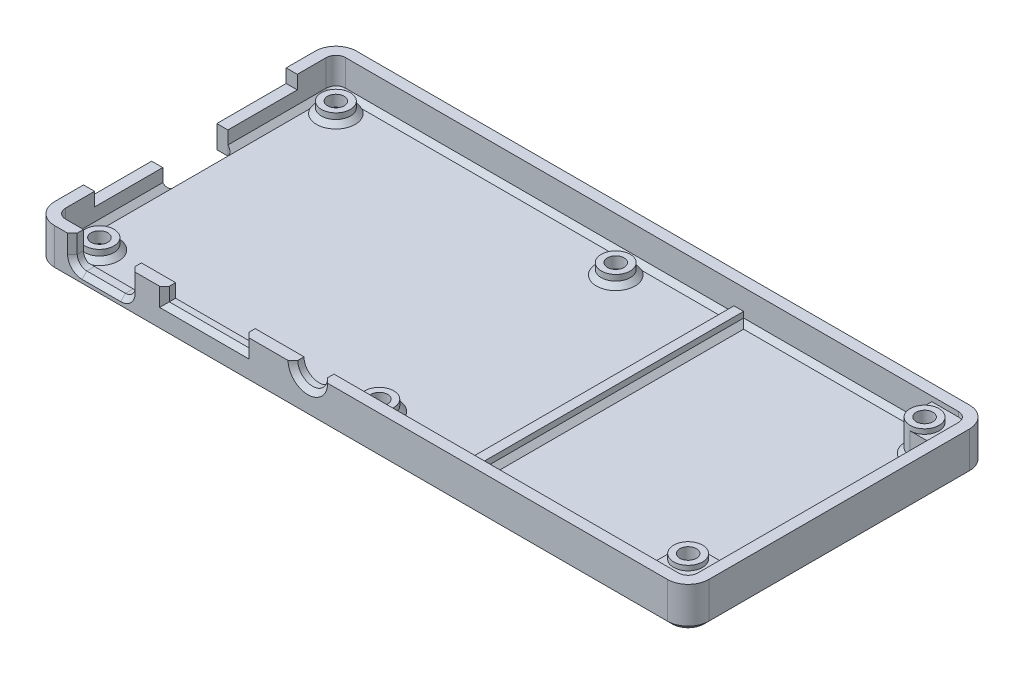
SolidWorks part; units mm, degrees
ref_plane "Front Plane" through (0, 0, 0) normal (0, 0, 1) x (1, 0, 0)
ref_plane "Top Plane" through (0, 0, 0) normal (0, 1, 0) x (1, 0, 0)
ref_plane "Right Plane" through (0, 0, 0) normal (1, 0, 0) x (0, 0, -1)
sketch "Sketch1" plane through (0, 0, 0) normal (0, 1, 0) x (1, 0, 0)
  line L0 (-71.5618, 3.106) -> (57.4382, 3.106) construction
  line L1 (-71.5618, 31.106) -> (57.4382, 31.106)
  line L2 (-71.5618, 31.106) -> (-71.5618, -24.894)
  line L3 (-71.5618, -24.894) -> (57.4382, -24.894)
  line L4 (57.4382, 31.106) -> (57.4382, -24.894)
  line L5 (-60.6618, -24.894) -> (-60.6618, -31.6828) construction
  line L6 (-68.0618, 27.606) -> (-10.0618, 27.606)
  line L7 (-68.0618, 27.606) -> (-68.0618, -21.394)
  line L8 (-68.0618, -21.394) -> (-10.0618, -21.394)
  line L9 (-10.0618, 27.606) -> (-10.0618, -21.394)
  line L10 (-39.5618, -24.894) -> (-39.5618, -31.6828) construction
  line L11 (-18.0618, -24.894) -> (-18.0618, -31.6828) construction
  line L12 (-65.4118, -26.5648) -> (-55.9118, -26.5648) construction
  line L13 (-48.0618, -26.5648) -> (-31.0618, -26.5648) construction
  line L14 (-22.0618, -26.5648) -> (-14.0618, -26.5648) construction
  line L15 (-72.5618, 9.606) -> (-72.5618, -3.394) construction
  line L16 (-71.5618, 3.106) -> (-72.5618, 3.106) construction
  dimension "D1" = 129
  dimension "D2" = 56
  dimension "D3" = 49
  dimension "D4" = 58
  dimension "D5" = 3.5
  dimension "D6" = 3.5
  dimension "D7" = 10.9
  dimension "D8" = 32
  dimension "D9" = 53.5
  dimension "D10" = 2
  dimension "D11" = 13
  dimension "D12" = 9.5
  dimension "D13" = 17
  dimension "D14" = 8
sketch "Sketch3" plane through (0, 0, 0) normal (0, 1, 0) x (1, 0, 0)
  line L4 (60.7382, 34.406) -> (-74.8618, 34.406)
  line L5 (-74.8618, 34.406) -> (-74.8618, -28.194)
  line L6 (-74.8618, -28.194) -> (60.7382, -28.194)
  line L7 (60.7382, -28.194) -> (60.7382, 34.406)
  line L8 (58.4382, 32.106) -> (-72.5618, 32.106)
  line L9 (58.4382, -25.894) -> (58.4382, 32.106)
  line L10 (-72.5618, -25.894) -> (58.4382, -25.894)
  line L11 (-72.5618, 32.106) -> (-72.5618, -25.894)
  line L12 (58.4382, 32.106) -> (-72.5618, 32.106)
  line L13 (58.4382, -25.894) -> (58.4382, 32.106)
  line L14 (-72.5618, -25.894) -> (58.4382, -25.894)
  line L15 (-72.5618, 32.106) -> (-72.5618, -25.894)
  line L16 (-7.0618, 3.106) -> (-7.0618, 34.406) construction
  line L17 (-71.5618, 3.106) -> (57.4382, 3.106) construction
  line L20 (-74.8618, 3.106) -> (52.7382, 3.106) construction
  line L25 (60.7382, -28.194) -> (60.7382, 34.406) construction
  line L26 (58.4382, -25.894) -> (58.4382, 32.106) construction
  dimension "D1" = 1
  dimension "D2" = 2.3
extrude "Boss-Extrude1" add sketch "Sketch3" along normal blind 8.5
sketch "Sketch5" plane through (0, 0, 0) normal (0, 1, 0) x (1, 0, 0)
  line L1 (-72.5618, 32.106) -> (58.4382, 32.106)
  line L2 (-72.5618, 32.106) -> (-72.5618, -25.894)
  line L3 (-72.5618, -25.894) -> (58.4382, -25.894)
  line L4 (58.4382, 32.106) -> (58.4382, -25.894)
extrude "Boss-Extrude2" add sketch "Sketch5" along normal blind 2
sketch "Sketch6" plane through (0, 2, 0) normal (0, 1, 0) x (1, 0, 0)
  circle A0 centre (-68.0618, 27.606) radius 3
  circle A1 centre (-68.0618, -21.394) radius 3
  circle A2 centre (-10.0618, -21.394) radius 3
  circle A3 centre (-10.0618, 27.606) radius 3
extrude "Boss-Extrude3" add sketch "Sketch6" along normal blind 2.2
sketch "Sketch10" plane through (0, 2, 0) normal (0, 1, 0) x (1, 0, 0)
  line L0 (58.4382, 32.106) -> (-72.5618, 32.106) construction
  line L1 (9.9382, 32.106) -> (11.9382, 32.106)
  line L2 (9.9382, 32.106) -> (9.9382, -25.894)
  line L3 (9.9382, -25.894) -> (11.9382, -25.894)
  line L4 (11.9382, 32.106) -> (11.9382, -25.894)
  line L5 (-72.5618, -25.894) -> (58.4382, -25.894) construction
  line L6 (-10.0618, 27.606) -> (-10.0618, -21.394) construction
  dimension "D1" = 2
  dimension "D2" = 20
extrude "Boss-Extrude4" add sketch "Sketch10" along normal blind 2.2
sketch "Sketch11" plane through (0, 0, 28.194) normal (0, 0, 1) x (1, 0, 0)
  line L0 (-74.8618, 8.5) -> (-74.8618, 0) construction
  line L1 (-66.8618, 8.5) -> (-54.8618, 8.5)
  line L2 (-66.8618, 8.5) -> (-66.8618, 2.7)
  line L3 (-66.8618, 2.7) -> (-54.8618, 2.7)
  line L4 (-54.8618, 8.5) -> (-54.8618, 2.7)
  line L5 (-74.8618, 0) -> (60.7382, 0) construction
  line L6 (-60.8618, 8.5) -> (-60.6618, 0) construction
  line L7 (-65.4118, 0) -> (-55.9118, 0) construction
  line L9 (-47.778, 8.5) -> (-31.278, 8.5)
  line L10 (-47.778, 8.5) -> (-47.778, 5.7)
  line L11 (-47.778, 5.7) -> (-31.278, 5.7)
  line L12 (-31.278, 8.5) -> (-31.278, 5.7)
  line L13 (-68.0618, 0) -> (-10.0618, 0) construction
  line L14 (-39.5618, 0) -> (-39.528, 8.5) construction
  line L15 (-48.0618, 0) -> (-31.0618, 0) construction
  line L16 (-18.0618, 0) -> (-18.0618, 8.5) construction
  line L17 (-22.0618, 0) -> (-14.0618, 0) construction
  line L18 (-74.8618, 8.5) -> (60.7382, 8.5) construction
  circle A0 centre (-18.0618, 8.5) radius 3.1
  dimension "D5" = 6.2
  dimension "D1" = 2.7
  dimension "D2" = 12
  dimension "D3" = 5.7
  dimension "D4" = 16.5
  dimension "D6" = 8
  dimension "D7" = 5.8
  dimension "D8" = 2.8
extrude "Cut-Extrude1" cut sketch "Sketch11" against normal up to next
sketch "Sketch12" plane through (-74.8618, 0, 0) normal (-1, 0, 0) x (0, 0, 1)
  line L0 (-3.106, 0) -> (-3.106, 8.5) construction
  line L1 (-27.606, 0) -> (21.394, 0) construction
  line L2 (-34.406, 8.5) -> (28.194, 8.5) construction
  line L3 (-24.106, 5.7) -> (17.894, 5.7)
  line L4 (-9.7329, 5.7) -> (3.7671, 5.7)
  line L5 (-9.7329, 5.7) -> (-9.7329, 2)
  line L6 (-9.7329, 2) -> (3.7671, 2)
  line L7 (3.7671, 5.7) -> (3.7671, 2)
  line L8 (-24.106, 8.5) -> (17.894, 8.5)
  line L9 (-24.106, 8.5) -> (-24.106, 5.7)
  line L11 (17.894, 8.5) -> (17.894, 5.7)
  line L12 (-9.7329, 3.85) -> (3.7671, 3.85) construction
  point P17 (-3.106, 5.7)
  dimension "D1" = 13.5
  dimension "D2" = 2.8
  dimension "D3" = 3.7
  dimension "D4" = 6.5
extrude "Cut-Extrude2" cut sketch "Sketch12" against normal up to next contours L9 L3 L11 L8 | L7 L6 L5 L4
fillet "Fillet6" radius 2 1 edges at (58.4382, 5.25, -32.106)
fillet "Fillet8" radius 2 2 edges at (-72.5618, 5.25, 25.894) (-72.5618, 5.25, -32.106)
chamfer "Chamfer1" distance 1 angle 45 4 edges at (-68.0618, 2, -24.606) (-68.0618, 2, 24.394) (-10.0618, 2, 24.394) (-10.0618, 2, -24.606)
sketch "Sketch24" plane through (0, 2, 0) normal (0, 1, 0) x (1, 0, 0)
  line L0 (11.9382, 3.106) -> (61.5789, 3.106) construction
  line L1 (11.9382, -25.894) -> (11.9382, 32.106) construction
  line L2 (53.9382, -18.394) -> (58.4382, -18.394)
  line L3 (58.4382, -25.894) -> (58.4382, 30.106) construction
  line L4 (-68.0618, 27.606) -> (-10.0618, 27.606) construction
  line L5 (-68.0618, 27.606) -> (-68.0618, -21.394) construction
  line L6 (-68.0618, -21.394) -> (-10.0618, -21.394) construction
  line L7 (-10.0618, 27.606) -> (-10.0618, -21.394) construction
  line L8 (-10.0618, 27.606) -> (53.9382, 27.606) construction
  line L9 (-10.0618, 27.606) -> (-10.0618, -21.394) construction
  line L10 (-10.0618, -21.394) -> (53.9382, -21.394) construction
  line L11 (53.9382, 27.606) -> (53.9382, -21.394) construction
  line L12 (50.9382, -21.394) -> (50.9382, -25.894)
  line L13 (11.9382, -25.894) -> (58.4382, -25.894) construction
  line L14 (58.4382, -25.894) -> (58.4382, 30.106) construction
  line L15 (58.4382, -18.394) -> (58.4382, -25.894)
  line L16 (58.4382, -25.894) -> (50.9382, -25.894)
  line L17 (50.9382, 27.606) -> (50.9382, 32.106)
  line L18 (56.4382, 32.106) -> (-70.5618, 32.106) construction
  line L19 (53.9382, 24.606) -> (58.4382, 24.606)
  line L20 (58.4382, 24.606) -> (58.4382, 32.106)
  line L21 (58.4382, 32.106) -> (50.9382, 32.106)
  arc A0 (50.9382, -21.394) -> (53.9382, -18.394) centre (53.9382, -21.394) cw
  arc A1 (50.9382, 27.606) -> (53.9382, 24.606) centre (53.9382, 27.606) ccw
  dimension "D2" = 4.5
extrude "Boss-Extrude7" add sketch "Sketch24" along normal up to surface (6.5 mm away) up to face at (-8.3784, 8.5, -11.175)
fillet "Fillet20" radius 4.3 4 edges at (60.7382, 4.25, 28.194) (-74.8618, 4.25, -34.406) (-74.8618, 4.25, 28.194) (60.7382, 4.25, -34.406)
chamfer "Chamfer5" distance 1 angle 45 18 edges at (-72.5618, 2, 13.8305) (-30.3118, 2, 25.894) (-72.5618, 2, -19.9195) (-71.976, 2, -31.5202) (-71.976, 2, 25.3082) (58.4382, 2, -3.106) (51.8169, 2, 19.2727) (50.9382, 2, 23.644) (56.1882, 2, 18.394) (31.4382, 2, -32.106) (51.8169, 2, -25.4847) (56.1882, 2, -24.606) (50.9382, 2, -29.856) (31.4382, 2, 25.894) (-30.3118, 2, -32.106) (9.9382, 2, -3.106) (11.9382, 2, -3.106) (-60.8618, 2.7, 25.894)
hole_wizard "CSK for #4 Flat Head Socket Cap Screw1" positions "Sketch28" profile "Sketch27" countersink size "#4" standard "ANSI Inch"
sketch "Sketch28" plane through (0, 0, 0) normal (0, -1, 0) x (-1, 0, 0)
  point P0 (68.0618, 27.606)
  point P4 (68.0618, -21.394)
  point P8 (-53.9382, 27.606)
  point P12 (-53.9382, -21.394)
  point P15 (10.0618, -21.394)
  point P19 (10.0618, 27.606)
sketch "Sketch27" plane through (-68.0618, 0, -27.606) normal (1, 0, 0) x (0, 0, -1)
  line L0 (0, 0) -> (0, 15.0378)
  line L1 (0, 15.0378) -> (1.7272, 14)
  line L2 (1.7272, 14) -> (1.7272, 1.8805)
  line L3 (1.7272, 1.8805) -> (3.3619, 0)
  line L5 (3.3619, 0) -> (0, 0)
  line L6 (-1.7272, 1.8805) -> (-3.3619, 0) construction
  line L10 (0, 15.0378) -> (-1.7272, 14) construction
  line L11 (0, -6.35) -> (0, 107.95) construction
  dimension "Hole Dia." = 3.4544
  dimension "Hole Depth" = 14
  dimension "Near C'Sink Dia." = 6.7238
  dimension "Near C'Sink Angle" = 82
  dimension "Drill Angle" = 118
chamfer "Chamfer7" distance 1 angle 45 8 edges at (-74.8618, 0, -3.106) (-73.6023, 0, 26.9346) (-73.6023, 0, -33.1466) (-7.0618, 0, 28.194) (-7.0618, 0, -34.406) (59.4788, 0, 26.9346) (59.4788, 0, -33.1466) (60.7382, 0, -3.106)
chamfer "Chamfer8" distance 1 angle 45 1 edges at (-74.8618, 2, -2.9829)
sketch "Sketch29" plane through (0, 8.5, 0) normal (0, 1, 0) x (1, 0, 0)
  line L0 (53.9382, 24.606) -> (58.4382, 24.606)
  line L1 (58.4382, 24.606) -> (58.4382, 30.106)
  line L2 (56.4382, 32.106) -> (50.9382, 32.106)
  line L3 (50.9382, 32.106) -> (50.9382, 27.606)
  line L4 (53.9382, -18.394) -> (58.4382, -18.394)
  line L5 (58.4382, -18.394) -> (58.4382, -23.894)
  line L6 (56.4382, -25.894) -> (50.9382, -25.894)
  line L7 (50.9382, -25.894) -> (50.9382, -21.394)
  arc A0 (53.9382, 24.606) -> (50.9382, 27.606) centre (53.9382, 27.606) ccw
  arc A1 (56.4382, 32.106) -> (58.4382, 30.106) centre (56.4382, 30.106) cw
  arc A2 (50.9382, -21.394) -> (53.9382, -18.394) centre (53.9382, -21.394) ccw
  arc A3 (56.4382, -25.894) -> (58.4382, -23.894) centre (56.4382, -23.894) ccw
extrude "Cut-Extrude3" cut sketch "Sketch29" against normal blind 1
fillet "Fillet21" radius 2 2 edges at (-54.8618, 2.7, 26.894) (-66.8618, 2.7, 26.894)
chamfer "Chamfer9" distance 1 angle 45 9 edges at (-18.0618, 5.4, 28.194) (-31.278, 7.1, 28.194) (-39.528, 5.7, 28.194) (-47.778, 7.1, 28.194) (-54.8618, 6.6, 28.194) (-55.4476, 3.2858, 28.194) (-60.8618, 2.7, 28.194) (-66.276, 3.2858, 28.194) (-66.8618, 6.6, 28.194)
sketch "Sketch30" plane through (0, 2, 0) normal (0, 1, 0) x (1, 0, 0)
  line L0 (-71.5618, -3.7671) -> (-71.5618, -19.4575) construction
  line L1 (-74.8618, 9.7329) -> (-71.5618, 9.7329)
  line L2 (-74.8618, 9.7329) -> (-74.8618, -3.7671)
  line L3 (-74.8618, -3.7671) -> (-71.5618, -3.7671)
  line L4 (-71.5618, 9.7329) -> (-71.5618, -3.7671)
  line L5 (-72.5618, -3.7671) -> (-71.5618, -3.7671) construction
extrude "Cut-Extrude4" cut sketch "Sketch30" against normal through all
fillet "Fillet22" radius 1 2 edges at (-71.5618, 1, -9.7329) (-71.5618, 1, 3.7671)
chamfer "Chamfer11" distance 1 angle 45 5 edges at (-73.2118, 0, 3.7671) (-73.2118, 0, -9.7329) (-71.8547, 0, 3.4742) (-71.8547, 0, -9.44) (-71.5618, 0, -2.9829)
